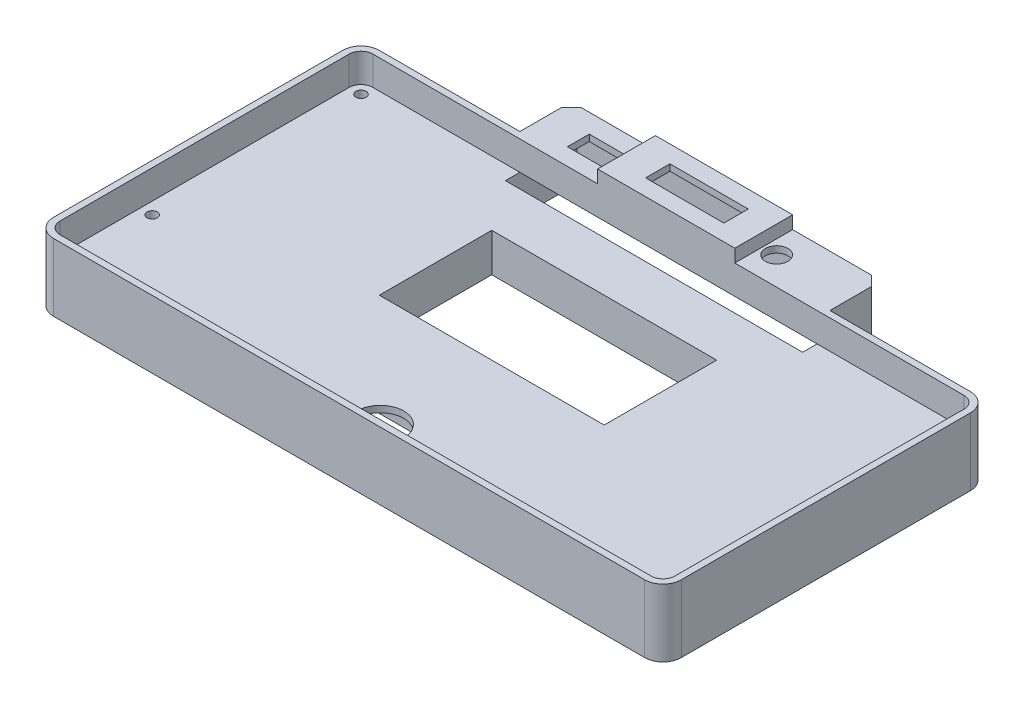
SolidWorks part; units mm, degrees
ref_plane "前视基准面" through (0, 0, 0) normal (0, 0, 1) x (1, 0, 0)
ref_plane "上视基准面" through (0, 0, 0) normal (0, 1, 0) x (1, 0, 0)
ref_plane "右视基准面" through (0, 0, 0) normal (1, 0, 0) x (0, 0, -1)
other "Configuration Table"
sketch "草图1" plane through (0, 0, 0) normal (0, 1, 0) x (1, 0, 0)
  line L1 (172.5, 94.5) -> (172.5, 99)
  line L2 (88, 91.5) -> (169.5, 91.5)
  line L3 (190.5, 91.5) -> (272, 91.5)
  line L4 (275.5, 95) -> (275.5, 185)
  line L6 (84.5, 185) -> (84.5, 95)
  line L8 (187.5, 99) -> (187.5, 94.5)
  line L9 (88, 188.5) -> (272, 188.5)
  arc A16 (180, 106.5) -> (172.5, 99) centre (180, 99) ccw
  arc A19 (187.5, 99) -> (180, 106.5) centre (180, 99) ccw
  arc A22 (187.5, 94.5) -> (190.5, 91.5) centre (190.5, 94.5) ccw
  arc A25 (169.5, 91.5) -> (172.5, 94.5) centre (169.5, 94.5) ccw
  arc A28 (272, 91.5) -> (275.5, 95) centre (272, 95) ccw
  arc A31 (275.5, 185) -> (272, 188.5) centre (272, 185) ccw
  arc A34 (88, 188.5) -> (84.5, 185) centre (88, 185) ccw
  arc A37 (84.5, 95) -> (88, 91.5) centre (88, 95) ccw
  circle A379 centre (88, 120) radius 1.6
  circle A384 centre (272, 185) radius 1.6
  circle A385 centre (88, 185) radius 1.6
extrude "凸台-拉伸1" add sketch "草图1" along normal blind 2
sketch "草图2" plane through (0, 2, 0) normal (0, 1, 0) x (1, 0, 0)
  line L1 (275.7, 95) -> (275.7, 185)
  line L2 (272, 188.7) -> (88, 188.7)
  line L3 (84.3, 185) -> (84.3, 95)
  line L7 (190.5, 91.5) -> (272, 91.5)
  line L8 (275.5, 95) -> (275.5, 185)
  line L9 (272, 188.5) -> (88, 188.5)
  line L10 (84.5, 185) -> (84.5, 95)
  line L11 (88, 91.5) -> (169.5, 91.5)
  line L12 (172.5, 94.5) -> (172.5, 99)
  line L13 (187.5, 99) -> (187.5, 94.5)
  line L14 (190.5, 91.5) -> (272, 91.5)
  line L15 (275.5, 95) -> (275.5, 185)
  line L16 (272, 188.5) -> (88, 188.5)
  line L17 (84.5, 185) -> (84.5, 95)
  line L18 (88, 91.5) -> (169.5, 91.5)
  line L19 (172.5, 94.5) -> (172.5, 99)
  line L20 (187.5, 99) -> (187.5, 94.5)
  line L22 (88, 91.3) -> (272, 91.3)
  line L23 (187.3, 99) -> (187.3, 94.5) construction
  line L24 (172.7, 94.5) -> (172.7, 99) construction
  line L25 (272, 91.3) -> (266.363, 95)
  line L32 (190.5, 91.3) -> (272, 91.3) construction
  line L33 (88, 91.3) -> (169.5, 91.3) construction
  arc A0 (272, 91.3) -> (275.7, 95) centre (272, 95) ccw
  arc A1 (275.7, 185) -> (272, 188.7) centre (272, 185) ccw
  arc A2 (88, 188.7) -> (84.3, 185) centre (88, 185) ccw
  arc A3 (84.3, 95) -> (88, 91.3) centre (88, 95) ccw
  arc A7 (187.5, 94.5) -> (190.5, 91.5) centre (190.5, 94.5) ccw
  arc A8 (272, 91.5) -> (275.5, 95) centre (272, 95) ccw
  arc A9 (275.5, 185) -> (272, 188.5) centre (272, 185) ccw
  arc A10 (88, 188.5) -> (84.5, 185) centre (88, 185) ccw
  arc A11 (84.5, 95) -> (88, 91.5) centre (88, 95) ccw
  arc A12 (169.5, 91.5) -> (172.5, 94.5) centre (169.5, 94.5) ccw
  arc A13 (187.5, 99) -> (172.5, 99) centre (180, 99) ccw
  arc A14 (187.5, 94.5) -> (190.5, 91.5) centre (190.5, 94.5) ccw
  arc A15 (272, 91.5) -> (275.5, 95) centre (272, 95) ccw
  arc A16 (275.5, 185) -> (272, 188.5) centre (272, 185) ccw
  arc A17 (88, 188.5) -> (84.5, 185) centre (88, 185) ccw
  arc A18 (84.5, 95) -> (88, 91.5) centre (88, 95) ccw
  arc A19 (169.5, 91.5) -> (172.5, 94.5) centre (169.5, 94.5) ccw
  arc A20 (187.5, 99) -> (172.5, 99) centre (180, 99) ccw
  circle A21 centre (180, 99) radius 7.3
  arc A22 (187.3, 99) -> (172.7, 99) centre (180, 99) ccw construction
  arc A23 (187.3, 94.5) -> (190.5, 91.3) centre (190.5, 94.5) ccw construction
  arc A24 (169.5, 91.3) -> (172.7, 94.5) centre (169.5, 94.5) ccw construction
  arc M32 (187.5, 94.5) -> (190.5, 91.5) centre (190.5, 94.5) ccw
  line M33 (190.5, 91.5) -> (272, 91.5)
  arc M34 (272, 91.5) -> (275.5, 95) centre (272, 95) ccw
  line M35 (275.5, 95) -> (275.5, 185)
  arc M36 (275.5, 185) -> (272, 188.5) centre (272, 185) ccw
  line M37 (272, 188.5) -> (88, 188.5)
  arc M38 (88, 188.5) -> (84.5, 185) centre (88, 185) ccw
  line M39 (84.5, 185) -> (84.5, 95)
  arc M40 (84.5, 95) -> (88, 91.5) centre (88, 95) ccw
  line M41 (88, 91.5) -> (169.5, 91.5)
  arc M42 (169.5, 91.5) -> (172.5, 94.5) centre (169.5, 94.5) ccw
  line M43 (172.5, 94.5) -> (172.5, 99)
  arc M44 (172.5, 99) -> (187.5, 99) centre (180, 99) cw
  line M45 (187.5, 99) -> (187.5, 94.5)
  dimension "D1" = 0
  dimension "D2" = 0.2
extrude "凸台-拉伸2" add sketch "草图2" against normal blind 2 contours L3 A3 A0 L1 A1 L2 A2 A21 M32 M45 M44 M43 M42 M41 M40 M39 M38 M37 M36 M35 M34 M33 region at (180, 2, -91.5148)
sketch "草图3" plane through (0, 2, 0) normal (0, 1, 0) x (1, 0, 0)
  line L0 (82.3, 185) -> (82.3, 95)
  line L4 (277.7, 95) -> (277.7, 185)
  line L5 (272, 190.7) -> (88, 190.7)
  line L6 (84.3, 185) -> (84.3, 95)
  line L7 (88, 91.3) -> (272, 91.3)
  line L8 (88, 91.3) -> (272, 91.3)
  line L9 (88, 89.3) -> (272, 89.3)
  line L10 (275.7, 95) -> (275.7, 185)
  line L11 (272, 188.7) -> (88, 188.7)
  line L12 (84.3, 185) -> (84.3, 95)
  line L16 (275.7, 95) -> (275.7, 185)
  line L17 (272, 188.7) -> (88, 188.7)
  line L24 (88, 91.3) -> (127.4996, 91.3) construction
  line L25 (127.4996, 91.3) -> (148.4998, 91.3) construction
  line L26 (148.4998, 91.3) -> (272, 91.3) construction
  line L27 (88, 89.3) -> (127.4996, 89.3) construction
  line L28 (127.4996, 89.3) -> (148.4998, 89.3) construction
  line L29 (148.4998, 89.3) -> (272, 89.3) construction
  arc A0 (82.3, 95) -> (88, 89.3) centre (88, 95) ccw
  arc A1 (272, 89.3) -> (277.7, 95) centre (272, 95) ccw
  arc A2 (277.7, 185) -> (272, 190.7) centre (272, 185) ccw
  arc A3 (88, 190.7) -> (82.3, 185) centre (88, 185) ccw
  arc A4 (84.3, 95) -> (88, 91.3) centre (88, 95) ccw
  arc A5 (272, 91.3) -> (275.7, 95) centre (272, 95) ccw
  arc A6 (275.7, 185) -> (272, 188.7) centre (272, 185) ccw
  arc A7 (88, 188.7) -> (84.3, 185) centre (88, 185) ccw
  arc A8 (84.3, 95) -> (88, 91.3) centre (88, 95) ccw
  arc A9 (272, 91.3) -> (275.7, 95) centre (272, 95) ccw
  arc A10 (275.7, 185) -> (272, 188.7) centre (272, 185) ccw
  arc A11 (88, 188.7) -> (84.3, 185) centre (88, 185) ccw
  dimension "D1" = 0
  dimension "D2" = 2
extrude "凸台-拉伸3" add sketch "草图3" along normal blind 2 and the other way blind 2
sketch "草图4" plane through (0, 4, 0) normal (0, 1, 0) x (1, 0, 0)
  line L0 (180, 190.7) -> (134.75, 190.7)
  line L1 (272, 190.7) -> (88, 190.7) construction
  line L2 (134.75, 190.7) -> (134.75, 188.7)
  line L3 (272, 188.7) -> (88, 188.7) construction
  line L4 (134.75, 188.7) -> (180, 188.7)
  line L5 (180, 188.7) -> (225.25, 188.7)
  line L6 (225.25, 188.7) -> (225.25, 190.7)
  line L7 (225.25, 190.7) -> (180, 190.7)
extrude "凸台-拉伸4" add sketch "草图4" along normal blind 11
sketch "草图5" plane through (0, 15, 0) normal (0, 1, 0) x (1, 0, 0)
  line L0 (180, 193.77) -> (192.19, 193.77)
  line L2 (180, 206.7) -> (134.75, 206.7)
  line L3 (134.75, 206.7) -> (134.75, 190.7)
  line L4 (134.75, 190.7) -> (225.25, 190.7)
  line L5 (225.25, 190.7) -> (225.25, 206.7)
  line L6 (225.25, 206.7) -> (180, 206.7)
  line L12 (192.19, 193.77) -> (192.19, 201.35)
  line L13 (192.19, 201.35) -> (167.81, 201.35)
  line L14 (167.81, 201.35) -> (167.81, 193.77)
  line L15 (167.81, 193.77) -> (180, 193.77)
extrude "凸台-拉伸5" add sketch "草图5" against normal blind 2
sketch "草图6" plane through (0, 4, 0) normal (0, 1, 0) x (1, 0, 0)
  line L12 (88, 89.3) -> (272, 89.3)
  line L13 (88, 89.3) -> (272, 89.3)
  line L14 (272, 91.3) -> (88, 91.3)
  line L15 (272, 91.3) -> (88, 91.3)
  line L16 (225.25, 190.7) -> (225.25, 188.7)
  line L17 (225.25, 188.7) -> (272, 188.7)
  line L18 (275.7, 185) -> (275.7, 95)
  line L22 (84.3, 95) -> (84.3, 185)
  line L23 (88, 188.7) -> (134.75, 188.7)
  line L24 (134.75, 188.7) -> (134.75, 190.7)
  line L25 (134.75, 190.7) -> (88, 190.7)
  line L26 (82.3, 185) -> (82.3, 95)
  line L30 (277.7, 95) -> (277.7, 185)
  line L31 (272, 190.7) -> (225.25, 190.7)
  line L32 (225.25, 190.7) -> (225.25, 188.7)
  line L33 (225.25, 188.7) -> (272, 188.7)
  line L34 (275.7, 185) -> (275.7, 95)
  line L38 (84.3, 95) -> (84.3, 185)
  line L39 (88, 188.7) -> (134.75, 188.7)
  line L40 (134.75, 188.7) -> (134.75, 190.7)
  line L41 (134.75, 190.7) -> (88, 190.7)
  line L42 (82.3, 185) -> (82.3, 95)
  line L46 (277.7, 95) -> (277.7, 185)
  line L47 (272, 190.7) -> (225.25, 190.7)
  arc A8 (275.7, 185) -> (272, 188.7) centre (272, 185) ccw
  arc A9 (272, 91.3) -> (275.7, 95) centre (272, 95) ccw
  arc A10 (84.3, 95) -> (88, 91.3) centre (88, 95) ccw
  arc A11 (88, 188.7) -> (84.3, 185) centre (88, 185) ccw
  arc A12 (88, 190.7) -> (82.3, 185) centre (88, 185) ccw
  arc A13 (82.3, 95) -> (88, 89.3) centre (88, 95) ccw
  arc A14 (272, 89.3) -> (277.7, 95) centre (272, 95) ccw
  arc A15 (277.7, 185) -> (272, 190.7) centre (272, 185) ccw
  arc A16 (275.7, 185) -> (272, 188.7) centre (272, 185) ccw
  arc A17 (272, 91.3) -> (275.7, 95) centre (272, 95) ccw
  arc A18 (84.3, 95) -> (88, 91.3) centre (88, 95) ccw
  arc A19 (88, 188.7) -> (84.3, 185) centre (88, 185) ccw
  arc A20 (88, 190.7) -> (82.3, 185) centre (88, 185) ccw
  arc A21 (82.3, 95) -> (88, 89.3) centre (88, 95) ccw
  arc A22 (272, 89.3) -> (277.7, 95) centre (272, 95) ccw
  arc A23 (277.7, 185) -> (272, 190.7) centre (272, 185) ccw
  dimension "D1" = 0
extrude "凸台-拉伸6" add sketch "草图6" along normal up to surface (11 mm away) up to face at (180, 15, -197.7)
sketch "草图7" plane through (0, 15, 0) normal (0, 1, 0) x (1, 0, 0)
  line L3 (134.75, 206.7) -> (134.75, 190.7)
  line L8 (134.75, 190.7) -> (131.75, 190.7)
  line L9 (134.75, 190.7) -> (88, 190.7) construction
  line L10 (131.75, 193.7) -> (131.75, 203.7)
  line L11 (131.75, 203.7) -> (134.75, 206.7)
  line L14 (131.75, 193.7) -> (131.75, 190.7)
  line L18 (228.25, 203.7) -> (225.25, 206.7)
  line L19 (228.25, 193.7) -> (228.25, 203.7)
  line L20 (225.25, 190.7) -> (228.25, 190.7)
  line L21 (225.25, 206.7) -> (225.25, 190.7)
  line L22 (228.25, 193.7) -> (228.25, 190.7)
extrude "凸台-拉伸7" add sketch "草图7" against normal blind 2
sketch "草图9" plane through (0, 13, 0) normal (0, -1, 0) x (1, 0, 0)
  line L0 (133.75, -190.7) -> (133.75, -202.8716)
  line L1 (133.75, -202.8716) -> (135.5784, -204.7)
  line L2 (135.5784, -204.7) -> (224.4216, -204.7)
  line L3 (224.4216, -204.7) -> (226.25, -202.8716)
  line L4 (226.25, -202.8716) -> (226.25, -190.7)
  line L5 (131.75, -190.7) -> (133.75, -190.7)
  line L6 (134.75, -206.7) -> (225.25, -206.7)
  line L7 (225.25, -206.7) -> (228.25, -203.7)
  line L8 (228.25, -203.7) -> (228.25, -190.7)
  line L9 (228.25, -190.7) -> (131.75, -190.7)
  line L10 (131.75, -190.7) -> (131.75, -203.7)
  line L11 (131.75, -203.7) -> (134.75, -206.7)
  line L12 (134.75, -206.7) -> (225.25, -206.7)
  line L13 (225.25, -206.7) -> (228.25, -203.7)
  line L14 (228.25, -203.7) -> (228.25, -190.7)
  line L16 (131.75, -190.7) -> (131.75, -203.7)
  line L17 (131.75, -203.7) -> (134.75, -206.7)
  line L18 (226.25, -190.7) -> (228.25, -190.7)
  dimension "D1" = 0
  dimension "D2" = 2
extrude "凸台-拉伸9" add sketch "草图9" along normal up to surface (13 mm away) up to face at (88, 0, -118.4)
sketch "草图10" plane through (0, 15, 0) normal (0, 1, 0) x (1, 0, 0)
  line L0 (131.75, 190.7) -> (131.75, 188.7)
  line L1 (272, 188.7) -> (88, 188.7) construction
  line L2 (131.75, 188.7) -> (88, 188.7)
  line L3 (275.7, 95) -> (275.7, 185) construction
  line L4 (84.3, 185) -> (84.3, 95) construction
  line L8 (275.7, 95) -> (275.7, 185)
  line L9 (84.3, 185) -> (84.3, 95)
  line L12 (272, 190.7) -> (228.25, 190.7)
  line L13 (228.25, 190.7) -> (228.25, 203.7)
  line L14 (228.25, 203.7) -> (225.25, 206.7)
  line L15 (225.25, 206.7) -> (134.75, 206.7)
  line L16 (134.75, 206.7) -> (131.75, 203.7)
  line L17 (131.75, 203.7) -> (131.75, 190.7)
  line L18 (131.75, 190.7) -> (88, 190.7)
  line L19 (82.3, 185) -> (82.3, 95)
  line L20 (88, 89.3) -> (272, 89.3)
  line L23 (277.7, 95) -> (277.7, 185)
  line L24 (272, 190.7) -> (228.25, 190.7)
  line L30 (131.75, 190.7) -> (88, 190.7)
  line L31 (82.3, 185) -> (82.3, 95)
  line L35 (277.7, 95) -> (277.7, 185)
  line L37 (272, 188.7) -> (228.25, 188.7)
  line L38 (88, 188.7) -> (272, 188.7) construction
  line L39 (228.25, 188.7) -> (228.25, 190.7)
  line L42 (88, 91.3) -> (272, 91.3)
  line L43 (88, 89.3) -> (272, 89.3)
  arc A0 (272, 91.3) -> (275.7, 95) centre (272, 95) ccw construction
  arc A1 (275.7, 185) -> (272, 188.7) centre (272, 185) ccw construction
  arc A2 (88, 188.7) -> (84.3, 185) centre (88, 185) ccw construction
  arc A3 (84.3, 95) -> (88, 91.3) centre (88, 95) ccw construction
  arc A4 (88, 190.7) -> (82.3, 185) centre (88, 185) ccw
  arc A5 (82.3, 95) -> (88, 89.3) centre (88, 95) ccw
  arc A6 (272, 89.3) -> (277.7, 95) centre (272, 95) ccw
  arc A7 (277.7, 185) -> (272, 190.7) centre (272, 185) ccw
  arc A8 (88, 190.7) -> (82.3, 185) centre (88, 185) ccw
  arc A9 (82.3, 95) -> (88, 89.3) centre (88, 95) ccw
  arc A10 (272, 89.3) -> (277.7, 95) centre (272, 95) ccw
  arc A11 (277.7, 185) -> (272, 190.7) centre (272, 185) ccw
  arc A12 (272, 91.3) -> (275.7, 95) centre (272, 95) ccw
  arc A13 (275.7, 185) -> (272, 188.7) centre (272, 185) ccw
  arc A14 (88, 188.7) -> (84.3, 185) centre (88, 185) ccw
  arc A15 (84.3, 95) -> (88, 91.3) centre (88, 95) ccw
  dimension "D1" = 0
extrude "切除-拉伸1" cut sketch "草图10" against normal blind 4
sketch "草图11" plane through (0, 0, 0) normal (0, -1, 0) x (1, 0, 0)
  line L0 (133.75, -190.7) -> (133.75, -184.2)
  line L1 (133.75, -184.2) -> (226.25, -184.2)
  line L2 (226.25, -184.2) -> (226.25, -190.7)
  line L3 (226.25, -190.7) -> (133.75, -190.7)
extrude "切除-拉伸2" cut sketch "草图11" against normal blind 2
sketch "草图12" plane through (0, 0, 0) normal (0, -1, 0) x (1, 0, 0)
  line L2 (180, -168.7) -> (215, -168.7)
  line L3 (215, -168.7) -> (215, -133.7)
  line L4 (215, -133.7) -> (145, -133.7)
  line L5 (145, -133.7) -> (145, -168.7)
  line L6 (145, -168.7) -> (180, -168.7)
extrude "切除-拉伸3" cut sketch "草图12" against normal through all
sketch "草图13" plane through (0, 0, 0) normal (0, -1, 0) x (1, 0, 0)
  line L14 (88, -190.7) -> (131.75, -190.7)
  line L15 (88, -188.7) -> (133.75, -188.7)
  line L16 (131.75, -190.7) -> (131.75, -203.7)
  line L17 (131.75, -203.7) -> (134.75, -206.7)
  line L18 (134.75, -206.7) -> (225.25, -206.7)
  line L19 (225.25, -206.7) -> (228.25, -203.7)
  line L20 (228.25, -203.7) -> (228.25, -190.7)
  line L21 (133.75, -188.7) -> (133.75, -202.8716)
  line L22 (228.25, -190.7) -> (272, -190.7)
  line L23 (277.7, -185) -> (277.7, -95)
  line L24 (272, -89.3) -> (88, -89.3)
  line L25 (272, -89.3) -> (88, -89.3)
  line L27 (82.3, -95) -> (82.3, -185)
  line L28 (88, -190.7) -> (131.75, -190.7)
  line L30 (131.75, -190.7) -> (131.75, -203.7)
  line L31 (131.75, -203.7) -> (134.75, -206.7)
  line L32 (134.75, -206.7) -> (225.25, -206.7)
  line L33 (225.25, -206.7) -> (228.25, -203.7)
  line L34 (228.25, -203.7) -> (228.25, -190.7)
  line L36 (228.25, -190.7) -> (272, -190.7)
  line L37 (277.7, -185) -> (277.7, -95)
  line L41 (82.3, -95) -> (82.3, -185)
  line L42 (133.75, -202.8716) -> (135.5784, -204.7)
  line L43 (135.5784, -204.7) -> (224.4216, -204.7)
  line L44 (224.4216, -204.7) -> (226.25, -202.8716)
  line L45 (226.25, -202.8716) -> (226.25, -188.7)
  line L46 (226.25, -188.7) -> (272, -188.7)
  line L47 (275.7, -185) -> (275.7, -95)
  line L48 (272, -91.3) -> (190.5, -91.3)
  line L49 (190.5, -91.3) -> (169.5, -91.3)
  line L50 (169.5, -91.3) -> (88, -91.3)
  line L51 (84.3, -95) -> (84.3, -185)
  line L64 (272, -89.3) -> (190.5, -89.3) construction
  line L65 (190.5, -89.3) -> (169.5, -89.3) construction
  line L66 (169.5, -89.3) -> (88, -89.3) construction
  arc A4 (82.3, -185) -> (88, -190.7) centre (88, -185) ccw
  arc A5 (272, -190.7) -> (277.7, -185) centre (272, -185) ccw
  arc A6 (277.7, -95) -> (272, -89.3) centre (272, -95) ccw
  arc A7 (88, -89.3) -> (82.3, -95) centre (88, -95) ccw
  arc A8 (82.3, -185) -> (88, -190.7) centre (88, -185) ccw
  arc A9 (272, -190.7) -> (277.7, -185) centre (272, -185) ccw
  arc A10 (277.7, -95) -> (272, -89.3) centre (272, -95) ccw
  arc A11 (88, -89.3) -> (82.3, -95) centre (88, -95) ccw
  arc A12 (272, -188.7) -> (275.7, -185) centre (272, -185) ccw
  arc A13 (275.7, -95) -> (272, -91.3) centre (272, -95) ccw
  arc A14 (88, -91.3) -> (84.3, -95) centre (88, -95) ccw
  arc A15 (84.3, -185) -> (88, -188.7) centre (88, -185) ccw
  dimension "D1" = 0
  dimension "D2" = 2
extrude "凸台-拉伸10" add sketch "草图13" along normal blind 10
sketch "草图14" plane through (0, 15, 0) normal (0, 1, 0) x (1, 0, 0)
  line L4 (143.25, 194) -> (156.25, 194)
  line L5 (156.25, 194) -> (156.25, 200.8)
  line L6 (156.25, 200.8) -> (143.25, 200.8)
  line L7 (143.25, 200.8) -> (143.25, 194)
  circle A0 centre (204.97, 197.4) radius 3.5
extrude "切除-拉伸4" cut sketch "草图14" against normal through all
sketch "草图16" plane through (0, 13, 0) normal (0, -1, 0) x (1, 0, 0)
  line L0 (133.75, -190.7) -> (159.95, -190.7)
  line L1 (159.95, -190.7) -> (159.95, -204.7)
  line L2 (135.5784, -204.7) -> (224.4216, -204.7) construction
  line L3 (159.95, -204.7) -> (135.5784, -204.7)
  line L4 (135.5784, -204.7) -> (133.75, -202.8716)
  line L5 (133.75, -202.8716) -> (133.75, -190.7)
  line L13 (226.25, -190.7) -> (198.65, -190.7)
  line L14 (133.75, -190.7) -> (226.25, -190.7) construction
  line L15 (198.65, -190.7) -> (198.65, -204.7)
  line L16 (198.65, -204.7) -> (224.4216, -204.7)
  line L17 (224.4216, -204.7) -> (226.25, -202.8716)
  line L18 (226.25, -202.8716) -> (226.25, -190.7)
  line L19 (156.25, -200.8) -> (143.25, -200.8) construction
  line L20 (143.25, -200.8) -> (143.25, -194) construction
  line L21 (143.25, -194) -> (156.25, -194) construction
  line L22 (156.25, -194) -> (156.25, -200.8) construction
  line L23 (156.25, -200.8) -> (143.25, -200.8)
  line L24 (143.25, -200.8) -> (143.25, -194)
  line L25 (143.25, -194) -> (156.25, -194)
  line L26 (156.25, -194) -> (156.25, -200.8)
  circle A0 centre (204.97, -197.4) radius 3.5 construction
  circle A1 centre (204.97, -197.4) radius 3.5
extrude "凸台-拉伸12" add sketch "草图16" along normal blind 4
sketch "草图17" plane through (0, 15, 0) normal (0, 1, 0) x (1, 0, 0)
  line L4 (200.65, 188.7) -> (200.65, 206.7)
  line L5 (131.75, 188.7) -> (228.25, 188.7) construction
  line L6 (157.95, 188.7) -> (157.95, 206.7)
  line L7 (225.25, 206.7) -> (134.75, 206.7) construction
  line L8 (157.95, 206.7) -> (134.75, 206.7)
  line L9 (134.75, 206.7) -> (131.75, 203.7)
  line L10 (131.75, 203.7) -> (131.75, 188.7)
  line L11 (131.75, 188.7) -> (157.95, 188.7)
  line L12 (200.65, 206.7) -> (225.25, 206.7)
  line L13 (225.25, 206.7) -> (228.25, 203.7)
  line L14 (228.25, 203.7) -> (228.25, 188.7)
  line L15 (228.25, 188.7) -> (200.65, 188.7)
extrude "切除-拉伸5" cut sketch "草图17" against normal blind 4
sketch "草图18" plane through (0, 0, 0) normal (0, -1, 0) x (1, 0, 0)
  line L1 (162.07, -91.3) -> (162.07, -113.8)
  line L2 (215, -168.7) -> (215, -133.7) construction
  line L4 (230.8, -113.8) -> (162.07, -113.8)
  line L5 (230.8, -113.8) -> (230.8, -91.3)
  line L6 (215, -133.7) -> (145, -133.7) construction
  line L7 (145, -133.7) -> (145, -168.7) construction
  line L8 (145, -168.7) -> (215, -168.7) construction
  line L9 (215, -168.7) -> (215, -133.7)
  line L10 (215, -133.7) -> (145, -133.7)
  line L11 (145, -133.7) -> (145, -168.7)
  line L12 (145, -168.7) -> (215, -168.7)
  line L13 (226.25, -188.7) -> (226.25, -184.2) construction
  line L14 (226.25, -184.2) -> (133.75, -184.2) construction
  line L15 (133.75, -184.2) -> (133.75, -188.7) construction
  line L16 (226.25, -188.7) -> (226.25, -184.2)
  line L17 (226.25, -184.2) -> (133.75, -184.2)
  line L18 (133.75, -184.2) -> (133.75, -188.7)
  line L19 (272, -91.3) -> (190.5, -91.3) construction
  line L20 (169.5, -91.3) -> (88, -91.3) construction
  line L21 (275.7, -185) -> (275.7, -95) construction
  line L22 (226.25, -188.7) -> (272, -188.7) construction
  line L23 (84.3, -95) -> (84.3, -185) construction
  line L24 (88, -188.7) -> (133.75, -188.7) construction
  line L25 (272, -91.3) -> (230.8, -91.3)
  line L26 (162.07, -91.3) -> (88, -91.3)
  line L27 (275.7, -185) -> (275.7, -95)
  line L28 (226.25, -188.7) -> (272, -188.7)
  line L29 (84.3, -95) -> (84.3, -185)
  line L30 (88, -188.7) -> (133.75, -188.7)
  circle A0 centre (88, -185) radius 1.6 construction
  circle A1 centre (88, -185) radius 1.6
  circle A2 centre (88, -120) radius 1.6 construction
  circle A3 centre (88, -120) radius 1.6
  circle A4 centre (272, -185) radius 1.6 construction
  circle A5 centre (272, -185) radius 1.6
  arc A6 (275.7, -95) -> (272, -91.3) centre (272, -95) ccw construction
  arc A7 (88, -91.3) -> (84.3, -95) centre (88, -95) ccw construction
  arc A8 (272, -188.7) -> (275.7, -185) centre (272, -185) ccw construction
  arc A9 (84.3, -185) -> (88, -188.7) centre (88, -185) ccw construction
  arc A10 (275.7, -95) -> (272, -91.3) centre (272, -95) ccw
  arc A11 (88, -91.3) -> (84.3, -95) centre (88, -95) ccw
  arc A12 (272, -188.7) -> (275.7, -185) centre (272, -185) ccw
  arc A13 (84.3, -185) -> (88, -188.7) centre (88, -185) ccw
extrude "凸台-拉伸13" add sketch "草图18" along normal up to surface (10 mm away) up to face at (180, -10, -165.8714)
